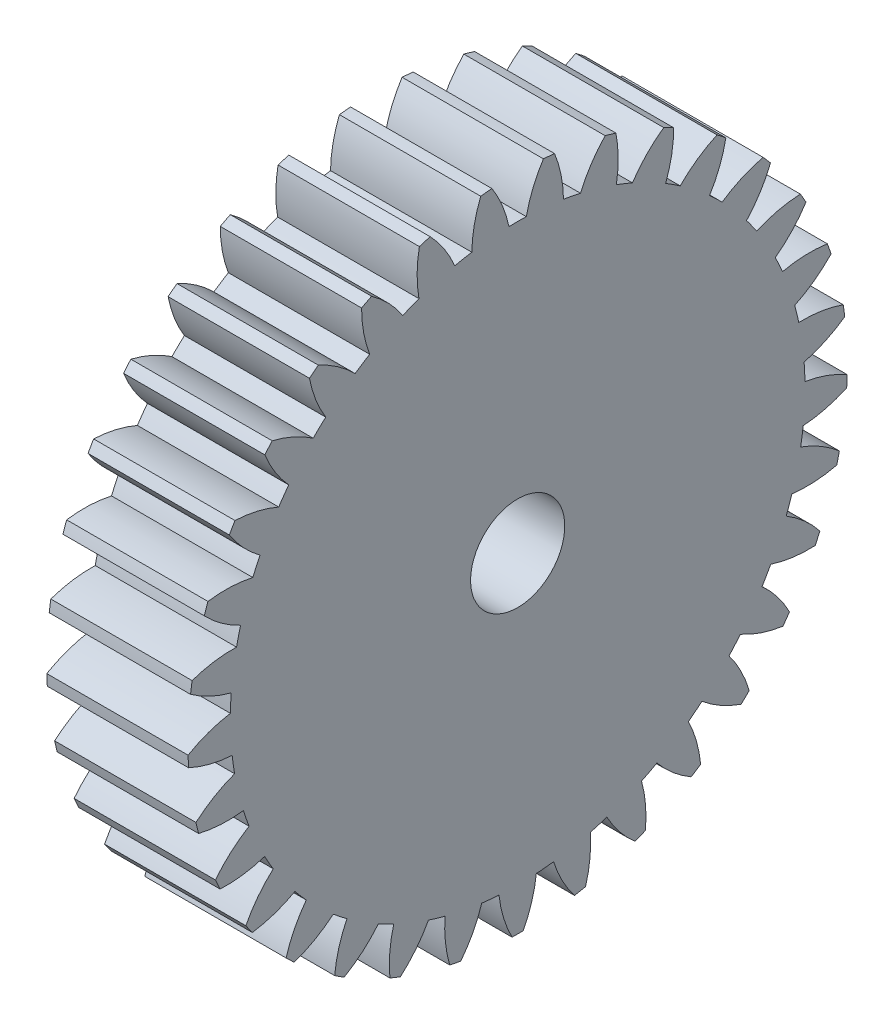
SolidWorks part; units mm, degrees
ref_plane "Plane1" through (0, 0, 0) normal (0, 0, 1) x (1, 0, 0)
ref_plane "Plane2" through (0, 0, 0) normal (0, 1, 0) x (1, 0, 0)
ref_plane "Plane3" through (0, 0, 0) normal (1, 0, 0) x (0, 0, -1)
sketch "HoldingSke" plane through (0, 0, 0) normal (0, 1, 0) x (1, 0, 0)
  line L0 (0, 0) -> (0.8387, -0.5446)
  line L1 (-15, 0) -> (100, 0) construction
  line L2 (0, 0) -> (-2.1039, 2.3779)
  line L3 (0, 0) -> (-11.863, 4.5341)
  line L4 (0, 0) -> (7.2428, 4.7035)
  line L5 (0, 0) -> (-46.8476, -17.4728)
  line L6 (0, 0) -> (-9.9476, -6.7116)
  line L7 (-2.1039, 2.3779) -> (8.6586, 51.2059)
  line L8 (-76.2, 54.61) -> (-75.3, 54.61)
  line L9 (-71.009, 38.7566) -> (-53.1078, 45.2721)
  line L10 (-76.2, 71.12) -> (104.1128, 71.12)
  line L11 (0, 0) -> (-12, 0)
  line L12 (-76.2, 101.6) -> (-76.162, 101.6)
  line L13 (24.9733, 27.94) -> (52.9518, 28.4284)
  line L14 (24.9733, 27.94) -> (24.9743, 27.94)
  line L15 (24.9733, 27.94) -> (100.4006, 29.5858)
  line L16 (-63.627, -1) -> (-12.827, -1)
  circle A0 centre (0, 0) radius 2.5
  circle A1 centre (0, 0) radius 15.249
  circle A2 centre (0, 0) radius 37.5
  circle A3 centre (0, 0) radius 2.5
  dimension "Num_teeth" = 33
  dimension "Pitch_radius" = 180.3128
  dimension "Width" = 12
sketch "BasProSke" plane through (0, 0, 0) normal (0, 1, 0) x (1, 0, 0)
  line L0 (-10, 0) -> (60, 0) construction
  line L1 (0, 0) -> (0, 17.5)
  line L2 (0, 0) -> (7.5, 0)
  line L3 (7.5, 0) -> (7.5, 17.5)
  line L4 (7.5, 17.5) -> (0, 17.5)
  dimension "Thickness" = 7.5
  dimension "Diameter" = 35
revolve "Base-Revolve" add sketch "BasProSke" angle 360 about L0
sketch "TooCutSke" plane through (0, 0, 0) normal (1, 0, 0) x (0, 0, -1)
  line L1 (0, 0) -> (0, 107) construction
  line L2 (0, 0) -> (-0.8516, 16.478) construction
  line L3 (0, 0) -> (-3.1339, 32.8194) construction
  line L4 (-0.8516, 16.478) -> (-1.5669, 16.4097) construction
  arc A0 (0.46, 15.2421) -> (-0.46, 15.2421) centre (0, 0) ccw
  arc A1 (1.3819, 17.4708) -> (-1.3819, 17.4708) centre (0, 0) ccw
  circle A2 centre (0, 0) radius 16.5 construction
  circle A3 centre (0, 0) radius 15.5049 construction
  arc A4 (-0.46, 15.2421) -> (-1.3819, 17.4708) centre (-6.9172, 13.8764) ccw
  arc A5 (1.3819, 17.4708) -> (0.46, 15.2421) centre (6.9172, 13.8764) ccw
extrude "ToothCut" cut sketch "TooCutSke" along normal through all
fillet "Breaks" [suppressed] radius 0.02 tangent propagation no
fillet "RootFillets" [suppressed] radius 0.251
pattern_circular "TeethCuts" count 33 every 10.909 about axis through (-10, 0, 0) along (1, 0, 0) of "ToothCut", "RootFillets", "Breaks"
sketch "HubNeaOneSke" plane through (0, 0, 0) normal (-1, 0, 0) x (0, 0, 1)
  circle A0 centre (0, 0) radius 15.249
  dimension "Diameter" = 30.498
extrude "HubNearOne" [suppressed] add sketch "HubNeaOneSke" along normal blind 42.5001
sketch "HubNeaBotSke" plane through (0, 0, 0) normal (-1, 0, 0) x (0, 0, 1)
  circle A0 centre (0, 0) radius 15.249
  dimension "Diameter" = 30.498
extrude "HubNearBoth" [suppressed] add sketch "HubNeaBotSke" along normal blind 21.25
ref_plane "FarPln" through (7.5, 0, 0) normal (1, 0, 0) x (0, 0, -1)
sketch "HubFarSke" plane through (7.5, 0, 0) normal (1, 0, 0) x (0, 0, -1)
  circle A0 centre (0, 0) radius 15.249
  dimension "Diameter" = 30.498
extrude "HubFar" [suppressed] add sketch "HubFarSke" along normal blind 21.25
sketch "BorSke" plane through (0, 0, 0) normal (1, 0, 0) x (0, 0, -1)
  circle A0 centre (0, 0) radius 2.5
  dimension "Diameter" = 5
extrude "Bore" cut sketch "BorSke" along normal mid plane 100.0001
sketch "KeySke" plane through (0, 0, 0) normal (1, 0, 0) x (0, 0, -1)
  line L0 (-1, 0) -> (-1, 3.4)
  line L1 (-1, 3.4) -> (1, 3.4)
  line L2 (1, 3.4) -> (1, 0)
  line L3 (0, 0) -> (0, 34) construction
  line L4 (-1, 0) -> (1, 0)
  dimension "Width" = 2
extrude "Keyway" [suppressed] cut sketch "KeySke" along normal mid plane 100.0001
pattern_circular "Keyway2" [suppressed] count 2 every 90 about axis through (-10, 0, 0) along (1, 0, 0) reverse direction yes
equation "' \"Module@HoldingSke\" = 6.35"
equation "' \"Num_teeth@HoldingSke\" = 12"
equation "' \"Ap@HoldingSke\" =  20"
equation "' \"Ap@HoldingSke\" = 20"
equation "' \"Width@HoldingSke\" = 0.5 * 25.4"
equation "' \"Hub_dia@HoldingSke\"= 1 * 25.4"
equation "' \"Hub_dia@HoldingSke\" = 1 * 25.4"
equation "' \"Overall_len@HoldingSke\" = 1.0 * 25.4"
equation "' \"Bore@HoldingSke\" = 0.75 * 25.4"
equation "' \"T_dim@HoldingSke\" = 0.1 * 25.4"
equation "' \"Width@KeySke\" = 0.25 * 25.4"
equation "' \"Show_teeth@HoldingSke\" = 13"
equation "' \"Backlash@HoldingSke\" = 0.009 * 25.4"
equation "' \"Addendum_fac@HoldingSke\" = 1.0"
equation "' \"Dedendum_fac@HoldingSke\" = 1.25"
equation "' \"Dedendum_add@HoldingSke\" = 0.00005 * 25.4"
equation "' \"Clearance_fac@HoldingSke\" = 0.25"
equation "\"Pitch@HoldingSke\" = 1 / \"Module@HoldingSke\""
equation "\"Overcut_dia@TooCutSke\" = (\"Num_teeth@HoldingSke\" + 2 * \"Addendum_fac@HoldingSke\") / \"Pitch@HoldingSke\" + 0.002 * 25.4"
equation "\"Pitch_dia@TooCutSke\" = \"Num_teeth@HoldingSke\" / \"Pitch@HoldingSke\""
equation "\"Base_dia@TooCutSke\" = \"Num_teeth@HoldingSke\" / \"Pitch@HoldingSke\" * cos((\"Ap@HoldingSke\"  * 3.14159265 / 180))"
equation "\"Root_dia@TooCutSke\" = (\"Num_teeth@HoldingSke\" + 2) / \"Pitch@HoldingSke\" - 2 * (\"Addendum_fac@HoldingSke\" + \"Dedendum_fac@HoldingSke\") / \"Pitch@HoldingSke\" - \"Dedendum_add@HoldingSke\" * 2"
equation "\"Half_ang@TooCutSke\" = 180 / \"Num_teeth@HoldingSke\""
equation "\"Half_CT@TooCutSke\" = \"Num_teeth@HoldingSke\" / \"Pitch@HoldingSke\" * sin((3.14159265 / 2 / \"Num_teeth@HoldingSke\")) / 2 - 7 * \"Backlash@HoldingSke\" / 4"
equation "\"Flank_rad@TooCutSke\" = \"Num_teeth@HoldingSke\" / \"Pitch@HoldingSke\" / 5"
equation "\"Radius@RootFillets\" = \"Clearance_fac@HoldingSke\" / \"Pitch@HoldingSke\" + \"Dedendum_add@HoldingSke\""
equation "\"Break_rad@Breaks\" = 0.02 / \"Pitch@HoldingSke\""
equation "\"Thickness@HoldingSke\" = \"Width@HoldingSke\""
equation "\"OAL@HoldingSke\" = \"Thickness@HoldingSke\""
equation "\"MHD@HoldingSke\" = (\"Num_teeth@HoldingSke\" + 2) / \"Pitch@HoldingSke\" - 2 * (\"Addendum_fac@HoldingSke\" + \"Dedendum_fac@HoldingSke\")  / \"Pitch@HoldingSke\" - \"Dedendum_add@HoldingSke\" * 2"
equation "\"MBD@HoldingSke\" = (\"Num_teeth@HoldingSke\" + 2) / \"Pitch@HoldingSke\" - 2 * (\"Addendum_fac@HoldingSke\" + \"Dedendum_fac@HoldingSke\")  / \"Pitch@HoldingSke\" - \"Dedendum_add@HoldingSke\" * 2 - 0.002 * 25.4"
equation "\"MHD@HoldingSke\" = ((sgn( \"MHD@HoldingSke\" - \"Hub_dia@HoldingSke\" )-1)*( \"MHD@HoldingSke\" - \"Hub_dia@HoldingSke\" ))/-2+ \"Hub_dia@HoldingSke\""
equation "\"MBD@HoldingSke\" = ((sgn( \"MBD@HoldingSke\" - \"Bore@HoldingSke\" )-1)*( \"MBD@HoldingSke\" - \"Bore@HoldingSke\" ))/-2+ \"Bore@HoldingSke\""
equation "\"OAL@HoldingSke\" = ((sgn( \"OAL@HoldingSke\" - \"Overall_len@HoldingSke\" )+1)*( \"OAL@HoldingSke\" - \"Overall_len@HoldingSke\" ))/2 + \"Overall_len@HoldingSke\" + 0.000002 * 25.4"
equation "\"Num_teeth@TeethCuts\" = int( \"Show_teeth@HoldingSke\" ) + 1"
equation "\"Num_teeth@TeethCuts\" = ((sgn( \"Num_teeth@TeethCuts\" - \"Num_teeth@HoldingSke\" )-1)*( \"Num_teeth@TeethCuts\" - \"Num_teeth@HoldingSke\" ))/-2+ \"Num_teeth@HoldingSke\""
equation "\"Num_teeth@TeethCuts\" = ((sgn( \"Num_teeth@TeethCuts\" - 2.0)+1)*( \"Num_teeth@TeethCuts\" - 2.0))/2 +2.0"
equation "\"Angle@TeethCuts\" = 360.0 / \"Num_teeth@HoldingSke\""
equation "\"Diameter@BasProSke\" = (\"Num_teeth@HoldingSke\" + 2 * \"Addendum_fac@HoldingSke\") / \"Pitch@HoldingSke\""
equation "\"Thickness@BasProSke\"=\"Thickness@HoldingSke\"- (4.5mm)"
equation "' \"Fillet_rad@BasProSke\" =  \"Thickness@HoldingSke\" * 0.05"
equation "' \"Fillet_rad@BasProSke\" = \"Thickness@HoldingSke\" * 0.05"
equation "\"MHD@HoldingSke\" = ((sgn( \"MHD@HoldingSke\" - \"Root_dia@TooCutSke\" )-1)*( \"MHD@HoldingSke\" - \"Root_dia@TooCutSke\" ))/-2+ \"Root_dia@TooCutSke\""
equation "\"Diameter@HubNeaOneSke\" = \"MHD@HoldingSke\""
equation "\"Length@HubNearOne\" = \"OAL@HoldingSke\" - \"Thickness@BasProSke\""
equation "\"Diameter@HubNeaBotSke\" = \"MHD@HoldingSke\""
equation "\"Length@HubNearBoth\" = ( \"OAL@HoldingSke\" - \"Thickness@BasProSke\" ) / 2.0"
equation "\"Thickness@FarPln\" = \"Thickness@BasProSke\""
equation "\"Diameter@HubFarSke\" = \"MHD@HoldingSke\""
equation "\"Length@HubFar\" = ( \"OAL@HoldingSke\" - \"Thickness@BasProSke\" ) / 2.0"
equation "\"Diameter@BorSke\" = \"MBD@HoldingSke\""
equation "\"D1@Bore\" = \"OAL@HoldingSke\" * 2.0"
equation "\"D1@Keyway\" = \"OAL@HoldingSke\" * 2.0"
equation "\"Offset@KeySke\" = \"T_dim@HoldingSke\" + \"MBD@HoldingSke\" / 2.0"
